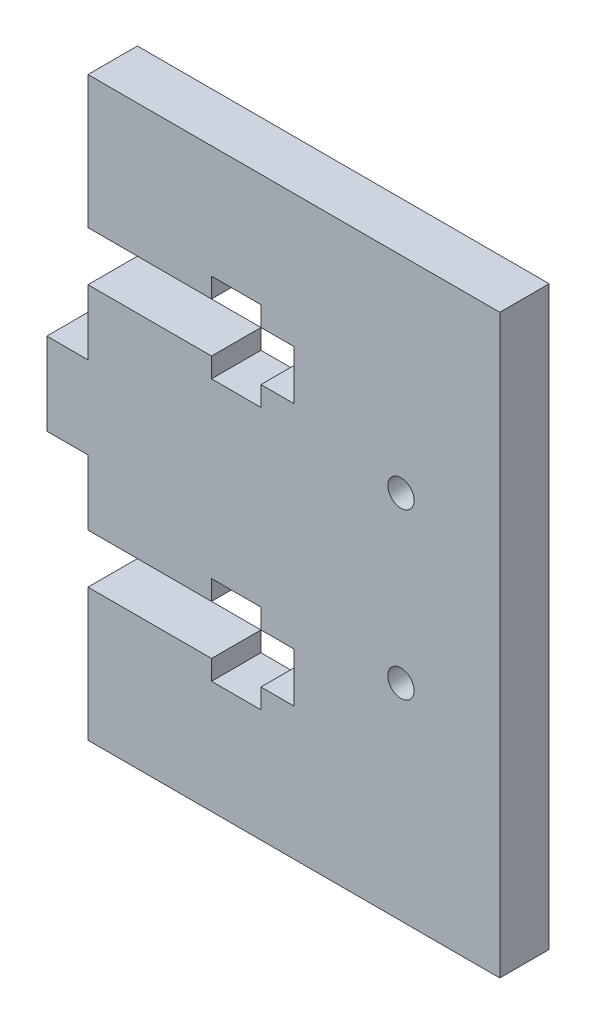
SolidWorks part; units mm, degrees
ref_plane "Front Plane" through (0, 0, 0) normal (0, 0, 1) x (1, 0, 0)
ref_plane "Top Plane" through (0, 0, 0) normal (0, 1, 0) x (1, 0, 0)
ref_plane "Right Plane" through (0, 0, 0) normal (1, 0, 0) x (0, 0, -1)
sketch "Sketch1" plane through (0, 0, 0) normal (0, 0, 1) x (1, 0, 0)
  line L0 (-97, 18.9) -> (-97, 21.3) construction
  line L1 (-68, -35) -> (-118, -35)
  line L2 (-68, -35) -> (-68, 35)
  line L3 (-68, 35) -> (-118, 35)
  line L4 (-118, -35) -> (-118, -18.9)
  line L5 (-68, -35) -> (-118, 35) construction
  line L6 (-68, 35) -> (-118, -35) construction
  line L7 (-93, 12.9) -> (-93, 18.9) construction
  line L8 (-97, 12.9) -> (-93, 12.9) construction
  line L9 (-97, 10.5) -> (-97, 12.9) construction
  line L10 (-103, 12.9) -> (-103, 10.5) construction
  line L11 (-103, 10.5) -> (-97, 10.5) construction
  line L12 (-118, 12.9) -> (-103, 12.9) construction
  line L13 (-103, 18.9) -> (-118, 18.9) construction
  line L14 (-103, 21.3) -> (-103, 18.9) construction
  line L15 (-97, 21.3) -> (-103, 21.3) construction
  line L16 (-93, 18.9) -> (-97, 18.9) construction
  line L17 (-97, 18.9) -> (-97, 21.3)
  line L18 (-93, 12.9) -> (-93, 18.9)
  line L19 (-97, 12.9) -> (-93, 12.9)
  line L20 (-97, 10.5) -> (-97, 12.9)
  line L21 (-103, 12.9) -> (-103, 10.5)
  line L22 (-103, 10.5) -> (-97, 10.5)
  line L23 (-118, 12.9) -> (-103, 12.9)
  line L24 (-103, 18.9) -> (-118, 18.9)
  line L25 (-103, 21.3) -> (-103, 18.9)
  line L26 (-97, 21.3) -> (-103, 21.3)
  line L27 (-93, 18.9) -> (-97, 18.9)
  line L28 (-118, 0) -> (-123, 0) construction
  line L29 (-118, 5) -> (-123, 5)
  line L30 (-118, -5) -> (-123, -5)
  line L31 (-123, 5) -> (-123, -5)
  line L32 (-118, 5) -> (-118, 12.9)
  line L38 (-97, -10.5) -> (-103, -10.5) construction
  line L39 (-97, -12.9) -> (-97, -10.5) construction
  line L40 (-93, -12.9) -> (-97, -12.9) construction
  line L41 (-103, -18.9) -> (-103, -21.3) construction
  line L42 (-93, -18.9) -> (-93, -12.9) construction
  line L43 (-97, -18.9) -> (-93, -18.9) construction
  line L44 (-97, -21.3) -> (-97, -18.9) construction
  line L45 (-103, -21.3) -> (-97, -21.3) construction
  line L46 (-118, -18.9) -> (-103, -18.9) construction
  line L47 (-103, -12.9) -> (-118, -12.9) construction
  line L48 (-103, -10.5) -> (-103, -12.9) construction
  line L49 (-103, -10.5) -> (-103, -12.9)
  line L50 (-97, -10.5) -> (-103, -10.5)
  line L51 (-97, -12.9) -> (-97, -10.5)
  line L52 (-93, -12.9) -> (-97, -12.9)
  line L53 (-103, -18.9) -> (-103, -21.3)
  line L54 (-93, -18.9) -> (-93, -12.9)
  line L55 (-97, -18.9) -> (-93, -18.9)
  line L56 (-97, -21.3) -> (-97, -18.9)
  line L57 (-103, -21.3) -> (-97, -21.3)
  line L58 (-118, -18.9) -> (-103, -18.9)
  line L59 (-103, -12.9) -> (-118, -12.9)
  line L60 (-118, -12.9) -> (-118, -5)
  line L61 (-118, 18.9) -> (-118, 35)
  circle A0 centre (-80, -10) radius 1.6 construction
  circle A1 centre (-80, 10) radius 1.6 construction
  circle A2 centre (-80, -10) radius 1.6
  circle A3 centre (-80, 10) radius 1.6
  point P0 (-93, 0)
  dimension "D1" = 50
  dimension "D2" = 5
  dimension "D3" = 5
  dimension "D4" = 5
extrude "Boss-Extrude1" add sketch "Sketch1" along normal blind 6
